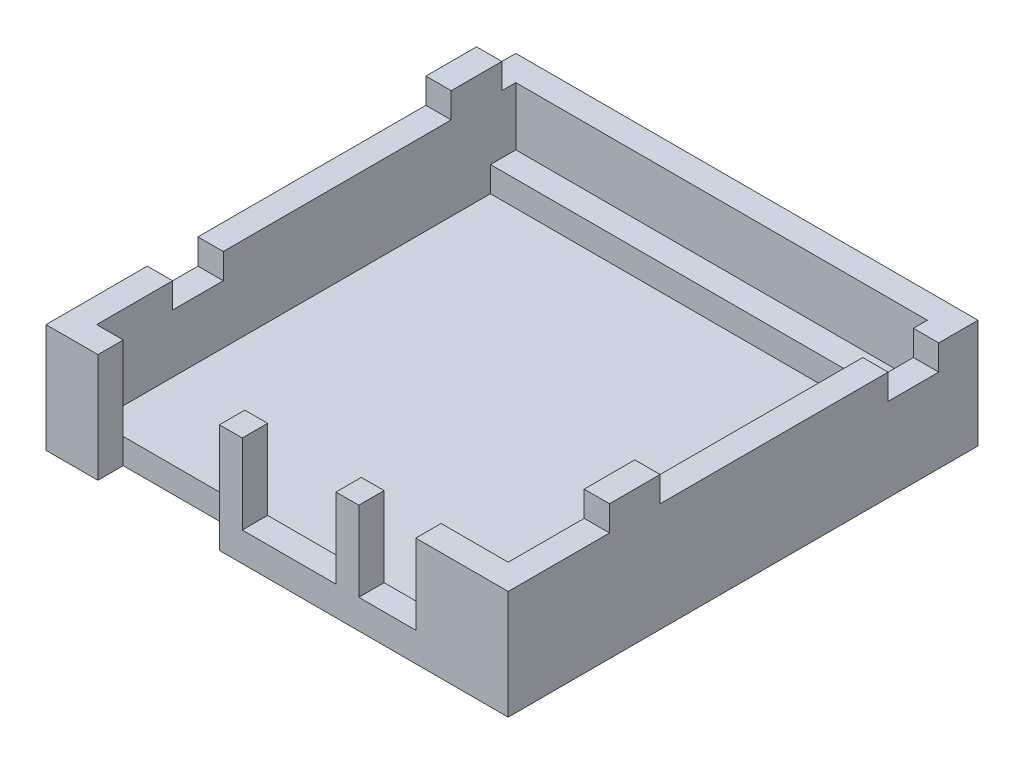
SolidWorks part; units mm, degrees
ref_plane "Front Plane" through (0, 0, 0) normal (0, 0, 1) x (1, 0, 0)
ref_plane "Top Plane" through (0, 0, 0) normal (0, 1, 0) x (1, 0, 0)
ref_plane "Right Plane" through (0, 0, 0) normal (1, 0, 0) x (0, 0, -1)
sketch "Sketch3" plane through (0, 0, 0) normal (0, 1, 0) x (1, 0, 0)
  line L1 (0, 0) -> (36.5, 0)
  line L2 (0, 0) -> (0, -37.1)
  line L3 (0, -37.1) -> (36.5, -37.1)
  line L4 (36.5, 0) -> (36.5, -37.1)
  dimension "D1" = 37.1
  dimension "D2" = 36.5
extrude "Shell" add sketch "Sketch3" along normal blind 8.6
sketch "Sketch4" plane through (0, 8.6, 0) normal (0, 1, 0) x (1, 0, 0)
  line L0 (36.5, 0) -> (0, 0) construction
  line L1 (2, -4) -> (34.5, -4)
  line L2 (2, -4) -> (2, -35.1)
  line L3 (2, -35.1) -> (34.5, -35.1)
  line L4 (34.5, -4) -> (34.5, -35.1)
  line L5 (36.5, -37.1) -> (36.5, 0) construction
  line L6 (0, 0) -> (0, -37.1) construction
  line L7 (0, -37.1) -> (36.5, -37.1) construction
  dimension "D1" = 4
  dimension "D2" = 2
  dimension "D3" = 2
  dimension "D4" = 2
extrude "Main Cavity" cut sketch "Sketch4" against normal offset from surface (6.6 mm away) 2 up to face at (18.25, 0, 18.55)
sketch "Sketch5" plane through (0, 8.6, 0) normal (0, 1, 0) x (1, 0, 0)
  line L0 (34.5, -35.1) -> (34.5, -4) construction
  line L1 (2, -4) -> (34.5, -4)
  line L2 (2, -4) -> (2, -2)
  line L3 (2, -2) -> (34.5, -2)
  line L4 (34.5, -4) -> (34.5, -2)
  dimension "D1" = 2
extrude "Support Shelf" cut sketch "Sketch5" against normal offset from surface (4.6 mm away) 2 up to face at (18.25, 2, 19.55)
sketch "Sketch6" plane through (0, 0, 37.1) normal (0, 0, 1) x (1, 0, 0)
  line L0 (0, 0) -> (36.5, 0) construction
  line L2 (29.2, 2.3) -> (29.2, 8.6)
  line L3 (29.2, 8.6) -> (24.7, 8.6)
  line L5 (0, 8.6) -> (36.5, 8.6) construction
  line L7 (22.9, 2.3) -> (22.9, 8.6)
  line L8 (22.9, 8.6) -> (15.5, 8.6)
  line L9 (15.5, 2.3) -> (15.5, 8.6)
  line L10 (13.7, 0) -> (4.1, 0)
  line L11 (13.7, 0) -> (13.7, 8.6)
  line L12 (13.7, 8.6) -> (4.1, 8.6)
  line L13 (4.1, 0) -> (4.1, 8.6)
  line L14 (0, 8.6) -> (0, 0) construction
  line L15 (15.5, 2.3) -> (22.9, 2.3)
  line L16 (24.7, 8.6) -> (24.7, 2.3)
  line L17 (24.7, 2.3) -> (29.2, 2.3)
  dimension "D1" = 4.1
  dimension "D2" = 4.5
  dimension "D3" = 7.4
  dimension "D4" = 1.8
  dimension "D5" = 1.8
  dimension "D6" = 9.6
  dimension "D7" = 2.3
  dimension "D8" = 2.3
extrude "Terminal Input" cut sketch "Sketch6" against normal up to surface (2 mm away) up to face at (18.25, 5.3, 35.1)
sketch "Sketch7" plane through (0, 8.6, 0) normal (0, 1, 0) x (1, 0, 0)
  line L0 (36.5, -37.1) -> (36.5, 0) construction
  line L1 (34.5, -25.1) -> (36.5, -25.1)
  line L2 (34.5, -25.1) -> (34.5, -29.1)
  line L3 (34.5, -29.1) -> (36.5, -29.1)
  line L4 (36.5, -25.1) -> (36.5, -29.1)
  line L5 (0, -3.1) -> (2, -3.1)
  line L6 (0, -3.1) -> (0, -7.1)
  line L7 (0, -7.1) -> (2, -7.1)
  line L8 (2, -3.1) -> (2, -7.1)
  line L9 (34.5, -35.1) -> (34.5, -2) construction
  line L10 (2, -2) -> (2, -35.1) construction
  line L11 (0, 0) -> (0, -37.1) construction
  line L12 (29.2, -37.1) -> (36.5, -37.1) construction
  line L13 (0, -37.1) -> (4.1, -37.1) construction
  dimension "D1" = 4
  dimension "D2" = 4
  dimension "D3" = 8
  dimension "D4" = 30
extrude "Male Tabs" add sketch "Sketch7" along normal blind 2
sketch "Sketch8" plane through (0, 8.6, 0) normal (0, 1, 0) x (1, 0, 0)
  line L0 (2, -3.1) -> (0, -3.1) construction
  line L1 (34.5, -3.1) -> (36.5, -3.1)
  line L2 (34.5, -3.1) -> (34.5, -7.1)
  line L3 (34.5, -7.1) -> (36.5, -7.1)
  line L4 (36.5, -3.1) -> (36.5, -7.1)
  line L5 (0, -25.1) -> (2, -25.1)
  line L6 (0, -25.1) -> (0, -29.1)
  line L7 (0, -29.1) -> (2, -29.1)
  line L8 (2, -25.1) -> (2, -29.1)
  line L9 (36.5, -25.1) -> (36.5, 0) construction
  line L11 (34.5, -4) -> (34.5, -35.1) construction
  line L12 (0, -7.1) -> (0, -37.1) construction
  line L13 (2, -7.1) -> (2, -35.1) construction
  line L14 (34.5, -29.1) -> (36.5, -29.1) construction
  dimension "D1" = 4
  dimension "D2" = 4
extrude "Female Tabs" cut sketch "Sketch8" against normal blind 2
